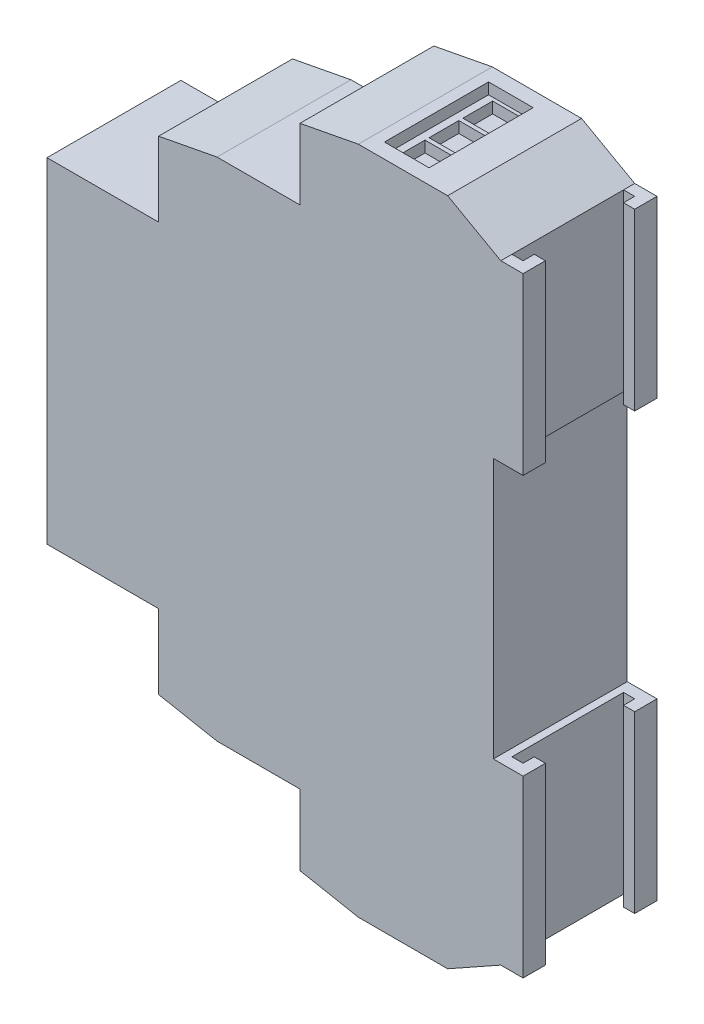
SolidWorks part; units mm, degrees
ref_plane "前视基准面" through (0, 0, 0) normal (0, 0, 1) x (1, 0, 0)
ref_plane "上视基准面" through (0, 0, 0) normal (0, 1, 0) x (1, 0, 0)
ref_plane "右视基准面" through (0, 0, 0) normal (1, 0, 0) x (0, 0, -1)
sketch "草图1" plane through (0, 0, 0) normal (0, 0, 1) x (1, 0, 0)
  line L0 (-52.4202, 0) -> (109.5479, 0) construction
  line L1 (0, -22.5) -> (0, 22.5)
  line L2 (0, 22.5) -> (15, 22.5)
  line L3 (15, 22.5) -> (15, 32.5)
  line L4 (22.8581, 34) -> (34, 34)
  line L5 (34, 34) -> (34, 43.5)
  line L6 (41.8581, 45) -> (53.8581, 45)
  line L7 (64, 41) -> (64, 17.5)
  line L8 (64, 17.5) -> (60, 17.5)
  line L9 (60, 17.5) -> (60, -17.5)
  line L10 (34, 43.5) -> (41.8581, 45)
  line L11 (15, 32.5) -> (22.8581, 34)
  line L12 (5, 22.5) -> (5, 0) construction
  line L13 (64, -17.5) -> (60, -17.5)
  line L16 (34, -43.5) -> (41.8581, -45)
  line L17 (34, -34) -> (34, -43.5)
  line L18 (22.8581, -34) -> (34, -34)
  line L19 (15, -32.5) -> (22.8581, -34)
  line L20 (15, -22.5) -> (15, -32.5)
  line L21 (0, -22.5) -> (15, -22.5)
  line L22 (64, 41) -> (61, 41)
  line L23 (61, 41) -> (53.8581, 45)
  line L24 (64, -41) -> (64, -17.5)
  line L25 (64, -41) -> (61, -41)
  line L26 (61, -41) -> (53.8581, -45)
  line L27 (41.8581, -45) -> (53.8581, -45)
  point P18 (60, 0)
  point P27 (0, 0)
  dimension "D1" = 15
  dimension "D2" = 19
  dimension "D3" = 30
  dimension "D4" = 45
  dimension "D5" = 65
  dimension "D6" = 90
  dimension "D7" = 4
  dimension "D8" = 8
  dimension "D9" = 8
  dimension "D10" = 5
  dimension "D11" = 35
  dimension "D12" = 1.5
  dimension "D13" = 1.5
  dimension "D14" = 3
  dimension "D15" = 4
  dimension "D16" = 12
extrude "凸台-拉伸1" add sketch "草图1" along normal mid plane 18
sketch "草图3" plane through (34, 0, 0) normal (-1, 0, 0) x (0, 0, 1)
  line L0 (0, 0) -> (0, -42.7477) construction
  line L1 (-5, -38) -> (5, -38) construction
  line L2 (-5, -35.5) -> (5, -35.5)
  line L3 (-5, -40.5) -> (5, -40.5)
  line L4 (9, -43.5) -> (-9, -43.5) construction
  arc A0 (-5, -35.5) -> (-5, -40.5) centre (-5, -38) ccw
  arc A1 (5, -40.5) -> (5, -35.5) centre (5, -38) ccw
  point P5 (0, -38)
  dimension "D1" = 5
  dimension "D2" = 10
  dimension "D3" = 3
extrude "切除-拉伸2" cut sketch "草图3" against normal blind 2.5
sketch "草图4" plane through (34, 0, 0) normal (-1, 0, 0) x (0, 0, 1)
  line L0 (0, 0) -> (0, 47.9279) construction
  line L1 (-5, 38) -> (5, 38) construction
  line L2 (-5, 40.5) -> (5, 40.5)
  line L3 (-5, 35.5) -> (5, 35.5)
  line L4 (9, 43.5) -> (-9, 43.5) construction
  arc A0 (-5, 40.5) -> (-5, 35.5) centre (-5, 38) ccw
  arc A1 (5, 35.5) -> (5, 40.5) centre (5, 38) ccw
  point P5 (0, 38)
  dimension "D1" = 5
  dimension "D2" = 10
  dimension "D3" = 3
extrude "切除-拉伸3" cut sketch "草图4" against normal blind 2.5
sketch "草图9" plane through (36.5, 0, 0) normal (-1, 0, 0) x (0, 0, 1)
  line L0 (0, 41.7802) -> (0, 34.4626) construction
  line L1 (-5, 35.5) -> (5, 35.5) construction
  line L2 (5, 40.5) -> (-5, 40.5) construction
  line L3 (-5, 35.5) -> (5, 35.5)
  line L4 (5, 40.5) -> (-5, 40.5)
  line L5 (-8.0838, 38) -> (8.1087, 38) construction
  arc A0 (5, 35.5) -> (5, 40.5) centre (5, 38) ccw construction
  arc A1 (-5, 40.5) -> (-5, 35.5) centre (-5, 38) ccw construction
  arc A2 (5, 35.5) -> (5, 40.5) centre (5, 38) ccw
  arc A3 (-5, 40.5) -> (-5, 35.5) centre (-5, 38) ccw
hole_wizard "打孔尺寸(%根据)开槽圆柱头螺钉的类型2" positions "草图10" profile "草图11" counterbore size "M2" standard "GB"
sketch "草图10" plane through (36.5, 0, 0) normal (-1, 0, 0) x (0, 0, 1)
  point P0 (0, 37.9857)
  point P2 (4.9851, 37.9857)
  point P4 (-4.9106, 37.9857)
sketch "草图11" plane through (36.5, 37.9857, 0) normal (0, 1, 0) x (0, 0, 1)
  line L0 (0, 0) -> (0, 8.221)
  line L1 (0, 8.221) -> (1.2, 7.5)
  line L2 (1.2, 7.5) -> (1.2, 2.3)
  line L3 (1.2, 2.3) -> (2.15, 2.3)
  line L4 (2.15, 2.3) -> (2.15, 0)
  line L5 (2.15, 0) -> (0, 0)
  line L10 (0, 8.221) -> (-1.2, 7.5) construction
  line L11 (0, -6.35) -> (0, 107.95) construction
  dimension "孔直径" = 2.4
  dimension "孔深度" = 7.5
  dimension "柱形沉头孔直径" = 4.3
  dimension "柱形沉头孔深度" = 2.3
  dimension "导头角度" = 118
hole_wizard "打孔尺寸(%根据)开槽圆柱头螺钉的类型4" positions "草图16" profile "草图17" counterbore size "M2" standard "GB"
sketch "草图16" plane through (36.5, 0, 0) normal (-1, 0, 0) x (0, 0, 1)
  point P0 (0, -38.0141)
  point P2 (-4.993, -38.0141)
  point P4 (4.9823, -38.0141)
sketch "草图17" plane through (36.5, -38.0141, 0) normal (0, 1, 0) x (0, 0, 1)
  line L0 (0, 0) -> (0, 8.221)
  line L1 (0, 8.221) -> (1.2, 7.5)
  line L2 (1.2, 7.5) -> (1.2, 2.3)
  line L3 (1.2, 2.3) -> (2.15, 2.3)
  line L4 (2.15, 2.3) -> (2.15, 0)
  line L5 (2.15, 0) -> (0, 0)
  line L10 (0, 8.221) -> (-1.2, 7.5) construction
  line L11 (0, -6.35) -> (0, 107.95) construction
  dimension "孔直径" = 2.4
  dimension "孔深度" = 7.5
  dimension "柱形沉头孔直径" = 4.3
  dimension "柱形沉头孔深度" = 2.3
  dimension "导头角度" = 118
sketch "文字151618" plane through (34, 0, 0) normal (-1, 0, 0) x (0, 0, 1)
  text T0 "15   16   18" font "汉仪长仿宋体" height 2
extrude "切除-拉伸6" cut sketch "文字151618" against normal blind 0.25
sketch "草图20" plane through (0, -34, 0) normal (0, -1, 0) x (1, 0, 0)
  line L0 (3.9329, 0) -> (47.7426, 0) construction
  line L1 (24.5, -7) -> (30.5, -7)
  line L2 (24.5, -7) -> (24.5, 7)
  line L3 (24.5, 7) -> (30.5, 7)
  line L4 (30.5, -7) -> (30.5, 7)
  line L5 (24.5, -7) -> (30.5, 7) construction
  line L6 (24.5, 7) -> (30.5, -7) construction
  line L7 (34, 9) -> (34, -9) construction
  point P0 (27.5, 0)
  dimension "D1" = 14
  dimension "D2" = 6
  dimension "D3" = 3.5
extrude "切除-拉伸7" cut sketch "草图20" against normal blind 1.5
sketch "草图21" plane through (0, -32.5, 0) normal (0, -1, 0) x (1, 0, 0)
  line L0 (25.5, -6.5) -> (25.5, -2.5)
  line L1 (25.5, 6.5) -> (29.5, 6.5)
  line L2 (25.5, 6.5) -> (25.5, 2.5)
  line L3 (25.5, 2.5) -> (29.5, 2.5)
  line L8 (30.5, -7) -> (30.5, 7) construction
  line L9 (24.5, -7) -> (30.5, -7) construction
  line L10 (24.5, 7) -> (24.5, -7) construction
  line L11 (30.5, 7) -> (24.5, 7) construction
  line L12 (30.5, -7) -> (30.5, 7)
  line L13 (24.5, -7) -> (30.5, -7)
  line L14 (24.5, 7) -> (24.5, -7)
  line L15 (30.5, 7) -> (24.5, 7)
  line L16 (27.5, 7) -> (27.5, -7) construction
  line L17 (24.5, 0) -> (30.5, 0) construction
  line L18 (29.5, 6.5) -> (29.5, 2.5)
  line L19 (25.5, 2) -> (29.5, 2)
  line L20 (25.5, 2) -> (25.5, -2)
  line L21 (25.5, -2) -> (29.5, -2)
  line L22 (29.5, 2) -> (29.5, -2)
  line L23 (25.5, 2) -> (29.5, -2) construction
  line L24 (25.5, -2) -> (29.5, 2) construction
  line L25 (25.5, 6.5) -> (29.5, 2.5) construction
  line L26 (25.5, 2.5) -> (29.5, 6.5) construction
  line L27 (25.5, -2.5) -> (29.5, -2.5)
  line L28 (29.5, -6.5) -> (29.5, -2.5)
  line L29 (25.5, -6.5) -> (29.5, -6.5)
  point P8 (27.5, 0)
  point P10 (27.5, 4.5)
  dimension "D1" = 1
  dimension "D2" = 0.5
extrude "切除-拉伸8" cut sketch "草图21" against normal blind 1.5 contours L1 L18 L3 L2 | L19 L22 L21 L20 | L27 L28 L29 L0
sketch "草图22" plane through (0, -45, 0) normal (0, -1, 0) x (1, 0, 0)
  line L0 (41.063, 0) -> (54.6105, 0) construction
  line L1 (24.5, 7) -> (24.5, -7) construction
  line L2 (49.3581, -7) -> (43.3581, -7)
  line L3 (49.3581, -7) -> (49.3581, 7)
  line L4 (49.3581, 7) -> (43.3581, 7)
  line L5 (43.3581, -7) -> (43.3581, 7)
  line L6 (49.3581, -7) -> (43.3581, 7) construction
  line L7 (49.3581, 7) -> (43.3581, -7) construction
  line L8 (30.5, 7) -> (24.5, 7) construction
  line L9 (53.8581, 9) -> (53.8581, -9) construction
  point P3 (46.3581, 0)
  dimension "D1" = 4.5
extrude "切除-拉伸9" cut sketch "草图22" against normal blind 1.5
sketch "草图23" plane through (0, -43.5, 0) normal (0, -1, 0) x (1, 0, 0)
  line L0 (49.3581, -7) -> (49.3581, 7) construction
  line L1 (43.3581, -7) -> (49.3581, -7) construction
  line L2 (43.3581, 7) -> (43.3581, -7) construction
  line L3 (49.3581, 7) -> (43.3581, 7) construction
  line L4 (49.3581, -7) -> (49.3581, 7)
  line L5 (43.3581, -7) -> (49.3581, -7)
  line L6 (43.3581, 7) -> (43.3581, -7)
  line L7 (49.3581, 7) -> (43.3581, 7)
  line L8 (46.3581, 7) -> (46.3581, -7) construction
  line L9 (43.3581, 0) -> (49.3581, 0) construction
  line L10 (29.5, 2) -> (29.5, -2) construction
  line L11 (44.3581, -2) -> (48.3581, -2)
  line L12 (44.3581, -2) -> (44.3581, 2)
  line L13 (44.3581, 2) -> (48.3581, 2)
  line L14 (48.3581, -2) -> (48.3581, 2)
  line L15 (44.3581, -2) -> (48.3581, 2) construction
  line L16 (44.3581, 2) -> (48.3581, -2) construction
  line L17 (44.3581, 2.5467) -> (48.3581, 2.5467)
  line L18 (44.3581, 2.5467) -> (44.3581, 6.5467)
  line L19 (44.3581, 6.5467) -> (48.3581, 6.5467)
  line L20 (48.3581, 2.5467) -> (48.3581, 6.5467)
  line L21 (44.3581, 2.5467) -> (48.3581, 6.5467) construction
  line L22 (44.3581, 6.5467) -> (48.3581, 2.5467) construction
  line L23 (25.5, 2) -> (29.5, 2) construction
  line L24 (25.5, 6.5) -> (29.5, 6.5) construction
  line L25 (29.5, 6.5) -> (29.5, 2.5) construction
  line L26 (48.3581, -2.5467) -> (48.3581, -6.5467)
  line L27 (44.3581, -2.5467) -> (48.3581, -2.5467)
  line L28 (44.3581, -2.5467) -> (44.3581, -6.5467)
  line L29 (44.3581, -6.5467) -> (48.3581, -6.5467)
  point P8 (46.3581, 0)
  point P13 (46.3581, 4.5467)
extrude "切除-拉伸10" cut sketch "草图23" against normal blind 1.5 contours L13 L14 L11 L12 | L17 L20 L19 L18 | L27 L26 L29 L28
sketch "草图24" plane through (0, 0, 0) normal (-1, 0, 0) x (0, 0, 1)
  line L0 (-9, 22.5) -> (-9, -22.5) construction
  line L1 (9, 22.5) -> (-9, 22.5) construction
  line L2 (9, 22.5) -> (-9, 22.5) construction
  line L3 (-3, 19.1674) -> (-3, 15.7865) construction
  line L4 (-1.5, 8.5) -> (-2.5, 8.5)
  line L5 (-1.5, 8.5) -> (-1.5, 12.5)
  line L6 (-1.5, 12.5) -> (-2.5, 12.5)
  line L7 (-2.5, 8.5) -> (-2.5, 12.5)
  line L8 (-1.5, 8.5) -> (-2.5, 12.5) construction
  line L9 (-1.5, 12.5) -> (-2.5, 8.5) construction
  line L10 (-4, 11) -> (0, 11)
  line L11 (-4, 11) -> (-4, 10)
  line L12 (-4, 10) -> (0, 10)
  line L13 (0, 11) -> (0, 10)
  line L14 (-4, 11) -> (0, 10) construction
  line L15 (-4, 10) -> (0, 11) construction
  line L16 (-0.5, 0.5) -> (0.5, 0.5)
  line L17 (-0.5, 0.5) -> (-0.5, 4.5)
  line L18 (-0.5, 4.5) -> (0.5, 4.5)
  line L19 (0.5, 0.5) -> (0.5, 4.5)
  line L20 (-0.5, 0.5) -> (0.5, 4.5) construction
  line L21 (-0.5, 4.5) -> (0.5, 0.5) construction
  line L22 (2, 3) -> (-2, 3)
  line L23 (2, 3) -> (2, 2)
  line L24 (2, 2) -> (-2, 2)
  line L25 (-2, 3) -> (-2, 2)
  line L26 (2, 3) -> (-2, 2) construction
  line L27 (2, 2) -> (-2, 3) construction
  line L28 (-3, 16.5) -> (-3, 18.5)
  line L29 (2.5, 19.1674) -> (2.5, 15.7865) construction
  line L30 (2.5, 18.5) -> (2.5, 16.5)
  circle A0 centre (-2, 10.5) radius 3
  circle A1 centre (0, 2.5) radius 3
  circle A2 centre (-3, 17.5) radius 1.5
  circle A3 centre (2.5, 17.5) radius 1.5
  arc A4 (-3, 18.5) -> (-3, 16.5) centre (-3, 17.5) ccw
  arc A5 (2.5, 18.5) -> (2.5, 16.5) centre (2.5, 17.5) ccw
  dimension "D3" = 6
  dimension "D6" = 3
  dimension "D13" = 1
  dimension "D1" = 7
  dimension "D2" = 12
  dimension "D4" = 9
  dimension "D5" = 20
  dimension "D7" = 5.5
  dimension "D8" = 6
  dimension "D9" = 5
  dimension "D10" = 5
  dimension "D11" = 1
  dimension "D12" = 4
extrude "切除-拉伸11" cut sketch "草图24" against normal blind 0.5 contours L5 L6 L7 L4 | L10 L13 L12 L11 | L17 L18 L19 L16 | L22 L25 L24 L23
extrude "切除-拉伸-薄壁1" cut sketch "草图24<3>" against normal blind 0.5 thin contours A0 | A1 thin type one direction reverse wall 0.25
sketch "草图24<3>" plane through (0, 0, 0) normal (-1, 0, 0) x (0, 0, 1) same geometry as "草图24"
extrude "切除-拉伸-薄壁2" cut sketch "草图24<4>" against normal blind 0.5 thin contours A2 | A3 thin type one direction reverse wall 0.25
sketch "草图24<4>" plane through (0, 0, 0) normal (-1, 0, 0) x (0, 0, 1) same geometry as "草图24"
revolve "旋转3" add sketch "草图24<7>" angle 180 about L3 reverse direction yes
sketch "草图24<7>" plane through (0, 0, 0) normal (-1, 0, 0) x (0, 0, 1) same geometry as "草图24"
revolve "旋转4" add sketch "草图24<8>" angle 180 about L29 reverse direction yes
sketch "草图24<8>" plane through (0, 0, 0) normal (-1, 0, 0) x (0, 0, 1) same geometry as "草图24"
sketch "文字Us" plane through (0, 0, 0) normal (-1, 0, 0) x (0, 0, 1)
  text T0 "Us" font "汉仪长仿宋体" height 2
sketch "文字R" plane through (0, 0, 0) normal (-1, 0, 0) x (0, 0, 1)
  text T0 "R" font "汉仪长仿宋体" height 2
extrude "切除-拉伸12" cut sketch "文字R" against normal blind 0.25
extrude "切除-拉伸13" cut sketch "文字Us" against normal blind 0.25
sketch "草图30" plane through (0, 45, 0) normal (0, 1, 0) x (1, 0, 0)
  line L4 (43.3581, 7) -> (43.3581, -7)
  line L5 (49.3581, 7) -> (43.3581, 7)
  line L6 (49.3581, -7) -> (49.3581, 7)
  line L7 (43.3581, -7) -> (49.3581, -7)
  line L8 (43.3581, 7) -> (43.3581, -7)
  line L9 (49.3581, 7) -> (43.3581, 7)
  line L10 (49.3581, -7) -> (49.3581, 7)
  line L11 (43.3581, -7) -> (49.3581, -7)
  dimension "D1" = 0
extrude "切除-拉伸15" cut sketch "草图30" against normal blind 1.5 contours L10 L9 L8 L11
sketch "草图32" plane through (0, 43.5, 0) normal (0, 1, 0) x (1, 0, 0)
  line L0 (44.3581, -6.5467) -> (44.3581, -2.5467) construction
  line L1 (44.3581, -2.5467) -> (48.3581, -2.5467) construction
  line L2 (48.3581, -2.5467) -> (48.3581, -6.5467) construction
  line L3 (48.3581, -6.5467) -> (44.3581, -6.5467) construction
  line L4 (44.3581, -2) -> (44.3581, 2) construction
  line L5 (44.3581, 2) -> (48.3581, 2) construction
  line L6 (48.3581, 2) -> (48.3581, -2) construction
  line L7 (48.3581, -2) -> (44.3581, -2) construction
  line L8 (44.3581, 2.5467) -> (44.3581, 6.5467) construction
  line L9 (44.3581, 6.5467) -> (48.3581, 6.5467) construction
  line L10 (48.3581, 6.5467) -> (48.3581, 2.5467) construction
  line L11 (48.3581, 2.5467) -> (44.3581, 2.5467) construction
  line L12 (44.3581, -6.5467) -> (44.3581, -2.5467)
  line L13 (44.3581, -2.5467) -> (48.3581, -2.5467)
  line L14 (48.3581, -2.5467) -> (48.3581, -6.5467)
  line L15 (48.3581, -6.5467) -> (44.3581, -6.5467)
  line L16 (44.3581, -2) -> (44.3581, 2)
  line L17 (44.3581, 2) -> (48.3581, 2)
  line L18 (48.3581, 2) -> (48.3581, -2)
  line L19 (48.3581, -2) -> (44.3581, -2)
  line L20 (44.3581, 2.5467) -> (44.3581, 6.5467)
  line L21 (44.3581, 6.5467) -> (48.3581, 6.5467)
  line L22 (48.3581, 6.5467) -> (48.3581, 2.5467)
  line L23 (48.3581, 2.5467) -> (44.3581, 2.5467)
extrude "切除-拉伸16" cut sketch "草图32" against normal blind 1.5
sketch "草图33" plane through (0, 17.5, 0) normal (0, -1, 0) x (1, 0, 0)
  line L0 (59.7593, 0) -> (65.1573, 0) construction
  line L1 (64, 6) -> (62.5, 6)
  line L2 (64, 9) -> (64, -9) construction
  line L3 (62.5, 6) -> (62.5, 7.5)
  line L4 (62.5, 7.5) -> (61, 7.5)
  line L5 (61, 9) -> (61, -9) construction
  line L6 (62.5, -7.5) -> (61, -7.5)
  line L7 (62.5, -6) -> (62.5, -7.5)
  line L8 (64, -6) -> (62.5, -6)
  line L9 (61, 7.5) -> (61, -7.5)
  line L10 (64, 6) -> (64, -6)
  dimension "D1" = 12
  dimension "D2" = 15
  dimension "D3" = 1.5
extrude "切除-拉伸17" cut sketch "草图33" against normal through all and the other way through all contours L10 L8 L7 L6 L9 L4 L3 L1
sketch "文字A1SA2" plane through (34, 0, 0) normal (-1, 0, 0) x (0, 0, 1)
  text T0 "A1   S   A2" font "汉仪长仿宋体" height 2
extrude "切除-拉伸18" cut sketch "文字A1SA2" against normal blind 0.25
sketch "文字GTR8-A1" plane through (0, 0, 0) normal (-1, 0, 0) x (0, 0, 1)
  text T0 "GTR8-A1" font "汉仪长仿宋体" height 2
extrude "切除-拉伸19" cut sketch "文字GTR8-A1" against normal blind 0.25
